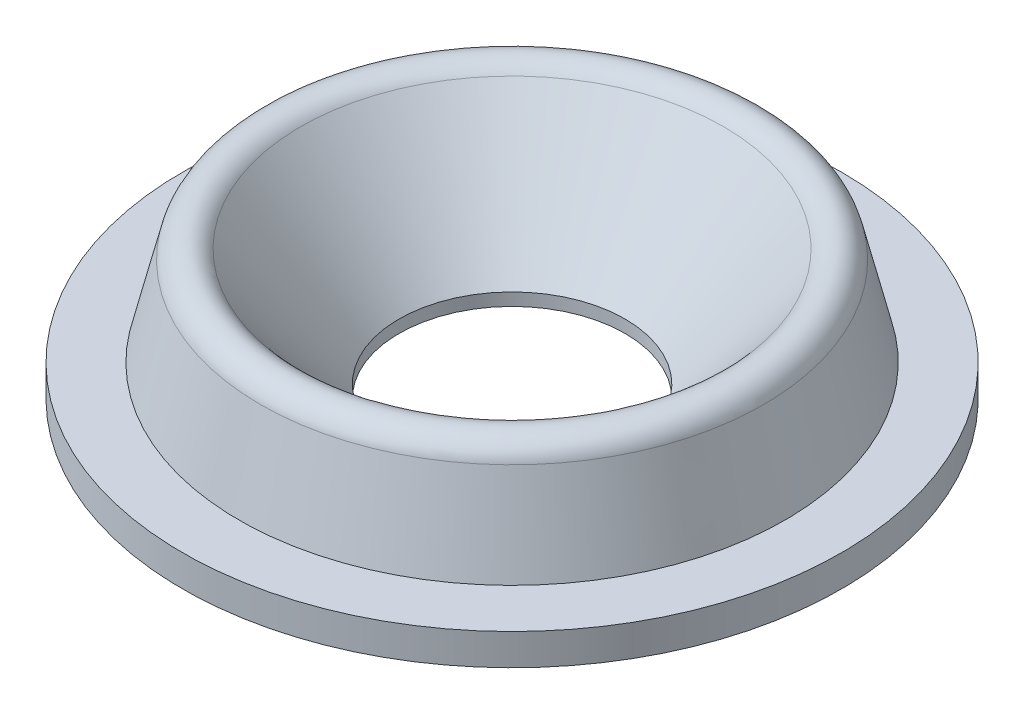
SolidWorks part; units mm, degrees
ref_plane "Front Plane" through (0, 0, 0) normal (0, 0, 1) x (1, 0, 0)
ref_plane "Top Plane" through (0, 0, 0) normal (0, 1, 0) x (1, 0, 0)
ref_plane "Right Plane" through (0, 0, 0) normal (1, 0, 0) x (0, 0, -1)
sketch "Sketch1" plane through (0, 0, 0) normal (0, 0, 1) x (1, 0, 0)
  line L0 (0, 0) -> (0, 3.4451) construction
  line L1 (-2.286, 0) -> (-2.286, 3.4451) construction
  line L2 (-6.6675, 0) -> (-6.6675, 0.635)
  line L3 (-6.6675, 0) -> (-6.6675, 3.4451) construction
  line L4 (-2.286, 0.254) -> (-4.2777, 2.6277)
  line L5 (-2.286, 0.254) -> (-2.286, 0)
  line L6 (-2.286, 0) -> (-6.6675, 0)
  line L7 (-6.6675, 0) -> (-2.286, 0) construction
  line L8 (-4.6345, 0) -> (-4.6345, 3.4451) construction
  line L9 (-6.6675, 0.635) -> (-5.5245, 0.635)
  line L10 (-5.5245, 0.635) -> (-5.087, 2.4381)
  arc A0 (-5.087, 2.4381) -> (-4.2777, 2.6277) centre (-4.6345, 2.3283) cw
  arc A1 (5.087, 2.4381) -> (4.2777, 2.6277) centre (4.6345, 2.3283) ccw construction
  dimension "D3" = 0.4657
  dimension "OD" = 13.335
  dimension "Height" = 2.794
  dimension "D2" = 40
  dimension "ID" = 4.572
  dimension "D1" = 0.254
  dimension "D4" = 0.635
  dimension "D5" = 11.049
revolve "Revolve1" add sketch "Sketch1" angle 360 about L0
shell "Shell2" thickness 0.7937 removed face at (0, 0, -2.286)
equation "\"D3@Sketch1\" = \"Height@Sketch1\"/6"
